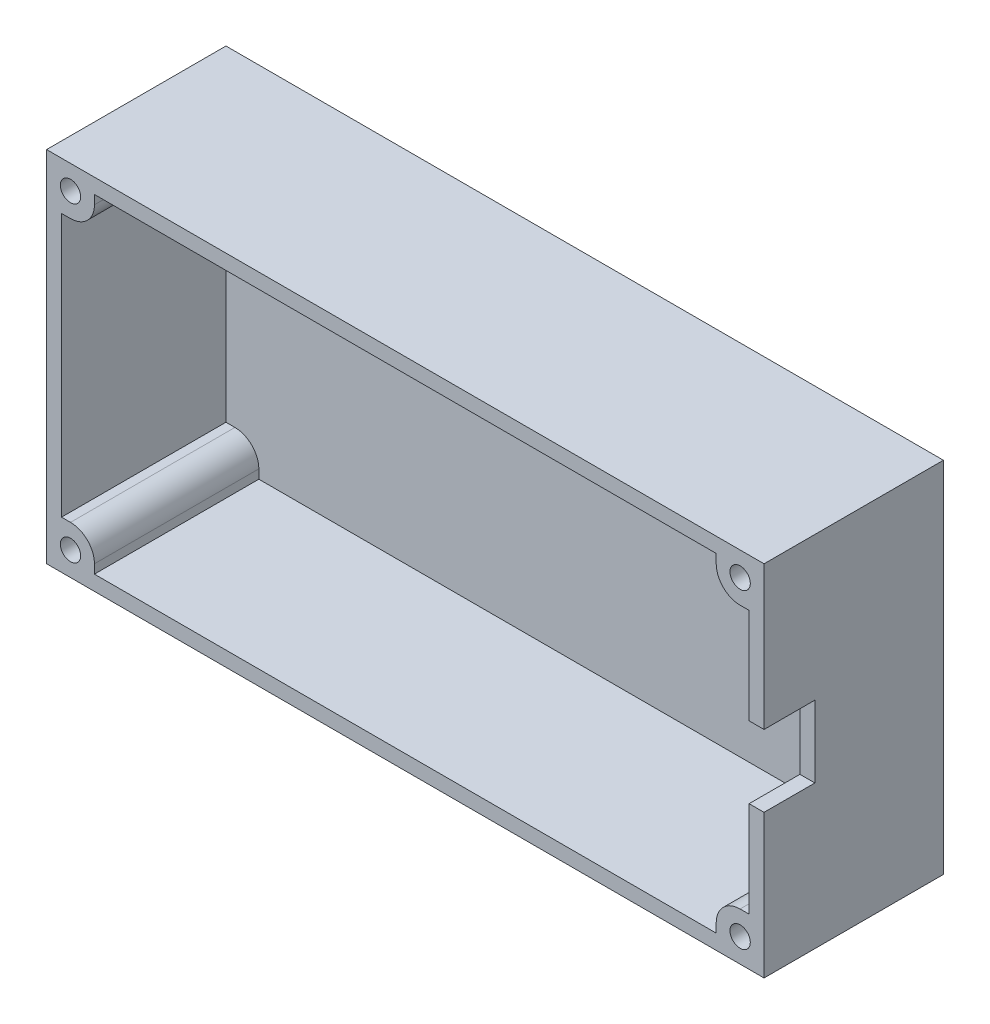
SolidWorks part; units mm, degrees
ref_plane "前视基准面" through (0, 0, 0) normal (0, 0, 1) x (1, 0, 0)
ref_plane "上视基准面" through (0, 0, 0) normal (0, 1, 0) x (1, 0, 0)
ref_plane "右视基准面" through (0, 0, 0) normal (1, 0, 0) x (0, 0, -1)
sketch "草图1" plane through (0, 0, 0) normal (0, 0, 1) x (1, 0, 0)
  line L0 (-52, 27.5) -> (52, 27.5)
  line L1 (-60, 30) -> (60, 30)
  line L2 (-60, 30) -> (-60, -30)
  line L3 (-60, -30) -> (60, -30)
  line L4 (60, 30) -> (60, -30)
  line L5 (-60, 30) -> (60, -30) construction
  line L6 (-60, -30) -> (60, 30) construction
  line L7 (57.5, 22) -> (57.5, -22)
  line L9 (-57.5, 22) -> (-57.5, -22)
  line L10 (-57.5, 22) -> (-56, 22)
  line L11 (-52, 26) -> (-52, 27.5)
  line L12 (52, 27.5) -> (52, 26)
  line L13 (56, 22) -> (57.5, 22)
  line L14 (57.5, -22) -> (56, -22)
  line L15 (52, -26) -> (52, -27.5)
  line L16 (-57.5, -22) -> (-56, -22)
  line L17 (-52, -26) -> (-52, -27.5)
  line L18 (-52, -27.5) -> (52, -27.5)
  line L19 (-57.5, 27.5) -> (-57.5, -27.5) construction
  line L21 (-57.5, -27.5) -> (57.5, -27.5) construction
  line L22 (57.5, 27.5) -> (57.5, -27.5) construction
  line L24 (-57.5, 27.5) -> (57.5, 27.5) construction
  arc A0 (52, 26) -> (56, 22) centre (56, 26) ccw
  arc A1 (56, -22) -> (52, -26) centre (56, -26) ccw
  arc A2 (-52, -26) -> (-56, -22) centre (-56, -26) ccw
  arc A3 (-52, 26) -> (-56, 22) centre (-56, 26) cw
  point P0 (0, 0)
  point P26 (52, -22)
  dimension "D4" = 4
  dimension "D1" = 120
  dimension "D2" = 60
  dimension "D3" = 2.5
extrude "凸台-拉伸1" add sketch "草图1" against normal blind 2.5 contours L2 L3 L4 L1
extrude "凸台-拉伸2" add sketch "草图1<3>" along normal blind 27.5
sketch "草图1<3>" plane through (0, 0, 0) normal (0, 0, 1) x (1, 0, 0) same geometry as "草图1"
sketch "草图2" plane through (0, 0, 27.5) normal (0, 0, 1) x (1, 0, 0)
  circle A0 centre (-56, 26) radius 1.7
  circle A1 centre (56, 26) radius 1.7
  circle A2 centre (56, -26) radius 1.7
  circle A3 centre (-56, -26) radius 1.7
  dimension "D1" = 3.4
  dimension "D2" = 3.4
  dimension "D3" = 3.4
  dimension "D4" = 3.4
extrude "切除-拉伸1" cut sketch "草图2" against normal through all
sketch "草图3" plane through (0, 0, 0) normal (0, 0, 1) x (1, 0, 0)
  line L0 (53.5, 27.5) -> (53.5, -27.5) construction
  line L1 (52, 27.5) -> (-52, 27.5) construction
  line L2 (-52, -27.5) -> (52, -27.5) construction
  line L3 (57.5, -22) -> (57.5, 22) construction
  line L4 (52.5, 9.2) -> (53.5, 9.2)
  line L5 (52.5, 5.8) -> (53.5, 5.8)
  line L6 (52.5, -5.8) -> (53.5, -5.8)
  line L7 (52.5, -9.2) -> (53.5, -9.2)
  line L8 (-5, 27.5) -> (-5, -27.5) construction
  line L9 (-52, -27.5) -> (52, -27.5) construction
  arc A0 (53.5, 5.8) -> (53.5, 9.2) centre (53.5, 7.5) ccw
  arc A1 (53.5, -9.2) -> (53.5, -5.8) centre (53.5, -7.5) ccw
  arc A2 (52.5, 9.2) -> (52.5, 5.8) centre (52.5, 7.5) ccw
  arc A3 (52.5, -5.8) -> (52.5, -9.2) centre (52.5, -7.5) ccw
  circle A4 centre (-5, 7.5) radius 1.7
  point P12 (53.5, 0)
  dimension "D2" = 3.4
  dimension "D3" = 3.4
  dimension "D4" = 7.5
  dimension "D5" = 15
  dimension "D8" = 3.4
  dimension "D1" = 4
  dimension "D7" = 58.5
  dimension "D6" = 2
extrude "切除-拉伸2" cut sketch "草图3" against normal through all
sketch "草图4" plane through (0, 0, 0) normal (0, 0, 1) x (1, 0, 0)
  line L1 (-1.8, 7.5) -> (-3.4, 10.2713)
  line L2 (-3.4, 10.2713) -> (-6.6, 10.2713)
  line L3 (-6.6, 10.2713) -> (-8.2, 7.5)
  line L4 (-8.2, 7.5) -> (-6.6, 4.7287)
  line L5 (-6.6, 4.7287) -> (-3.4, 4.7287)
  line L6 (-3.4, 4.7287) -> (-1.8, 7.5)
  line L7 (56.2, 7.5) -> (54.6, 10.2713)
  line L8 (54.6, 10.2713) -> (51.4, 10.2713)
  line L9 (51.4, 10.2713) -> (49.8, 7.5)
  line L10 (49.8, 7.5) -> (51.4, 4.7287)
  line L11 (51.4, 4.7287) -> (54.6, 4.7287)
  line L12 (54.6, 4.7287) -> (56.2, 7.5)
  line L13 (56.2, -7.5) -> (54.6, -4.7287)
  line L14 (54.6, -4.7287) -> (51.4, -4.7287)
  line L15 (51.4, -4.7287) -> (49.8, -7.5)
  line L16 (49.8, -7.5) -> (51.4, -10.2713)
  line L17 (51.4, -10.2713) -> (54.6, -10.2713)
  line L18 (54.6, -10.2713) -> (56.2, -7.5)
  circle A0 centre (-5, 7.5) radius 2.7713 construction
  circle A1 centre (53, 7.5) radius 2.7713 construction
  circle A2 centre (53, -7.5) radius 2.7713 construction
  dimension "D1" = 3.2
  dimension "D2" = 3.2
  dimension "D3" = 3.2
extrude "切除-拉伸3" cut sketch "草图4" against normal blind 0.5
sketch "草图5" plane through (0, 0, 27.5) normal (0, 0, 1) x (1, 0, 0)
  line L0 (57.5, 0) -> (60, 0) construction
  line L1 (57.5, -22) -> (57.5, 22) construction
  line L2 (60, -30) -> (60, 30) construction
  line L4 (57.5, 6) -> (60, 6)
  line L5 (57.5, 6) -> (57.5, -6)
  line L6 (57.5, -6) -> (60, -6)
  line L7 (60, 6) -> (60, -6)
  line L8 (57.5, 6) -> (60, -6) construction
  line L9 (57.5, -6) -> (60, 6) construction
  point P6 (58.75, 0)
  dimension "D1" = 12
extrude "切除-拉伸4" cut sketch "草图5" against normal blind 8.5
sketch "草图6" plane through (0, 0, -2.5) normal (0, 0, -1) x (-1, 0, 0)
  circle A0 centre (-56, 26) radius 3
  circle A1 centre (-56, -26) radius 3
  circle A2 centre (56, -26) radius 3
  circle A3 centre (56, 26) radius 3
  dimension "D1" = 6
  dimension "D2" = 6
  dimension "D3" = 6
  dimension "D4" = 6
extrude "切除-拉伸5" cut sketch "草图6" against normal blind 15
chamfer "倒角1" distance 2 angle 45 4 edges at (-57.7, 26, 12.5) (-57.7, -26, 12.5) (54.3, -26, 12.5) (54.3, 26, 12.5)
